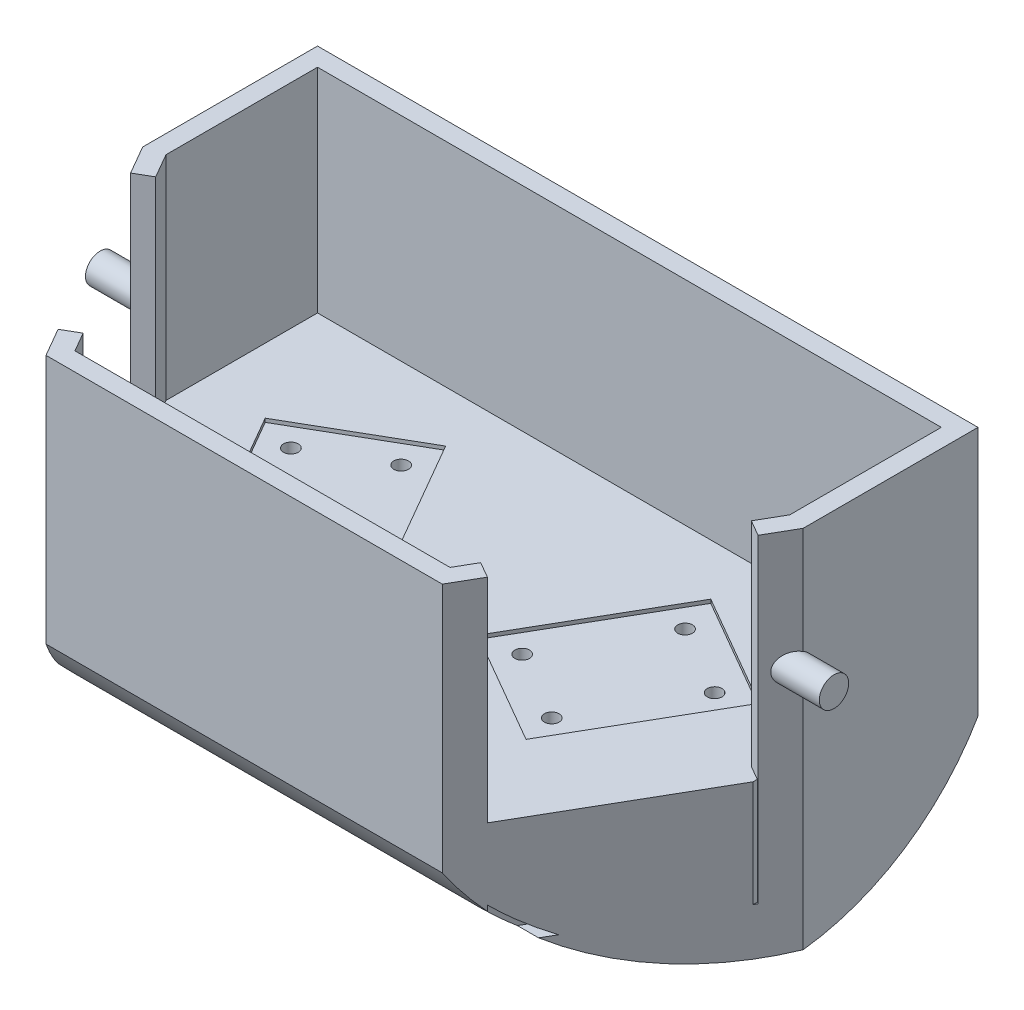
SolidWorks part; units mm, degrees
ref_plane "Front Plane" through (0, 0, 0) normal (0, 0, 1) x (1, 0, 0)
ref_plane "Top Plane" through (0, 0, 0) normal (0, 1, 0) x (1, 0, 0)
ref_plane "Right Plane" through (0, 0, 0) normal (1, 0, 0) x (0, 0, -1)
sketch "Sketch2" plane through (0, 0, 0) normal (0, 1, 0) x (1, 0, 0)
  line L0 (-54, -55) -> (-90, 7.3538)
  line L1 (-90, -55) -> (90, -55)
  line L2 (-90, -55) -> (-90, 55)
  line L3 (-90, 55) -> (90, 55)
  line L4 (90, -55) -> (90, 55)
  line L5 (-90, -55) -> (90, 55) construction
  line L6 (-90, 55) -> (90, -55) construction
  line L7 (0, -55) -> (0, 55) construction
  line L8 (54, -55) -> (90, 7.3538)
  point P0 (0, 0)
  dimension "D1" = 110
  dimension "D2" = 180
  dimension "D3" = 72
  dimension "D4" = 30
extrude "Boss-Extrude1" add sketch "Sketch2" along normal blind 50 and the other way blind 50 contours L1 L8 L4 L3 L2 L0 region at (0, 0, -4.375)
sketch "Sketch13" plane through (-90, 0, 0) normal (-1, 0, 0) x (0, 0, 1)
  line L0 (55, -50) -> (55, 50) construction
  line L1 (-55, -50) -> (55, -50)
  line L2 (-55, -50) -> (-55, -18.1472)
  line L3 (-55, -18.1472) -> (55, -18.1472)
  line L4 (55, -50) -> (55, -18.1472)
  line L5 (-55, -18.1472) -> (-55, -50)
  line L6 (-55, -50) -> (55, -50)
  line L7 (55, -50) -> (55, -18.1472)
  arc A1 (-55, -18.1472) -> (55, -18.1472) centre (0, 13.61) ccw
  point P8 (0, -49.9)
  line M1 (-7.3538, -50) -> (-7.3538, 50)
  line M3 (-55, 50) -> (-55, -50)
  line M4 (-55, -50) -> (-7.3538, -50)
  dimension "D1" = 63.51
  dimension "D2" = 0.1
extrude "Cut-Extrude9" cut sketch "Sketch13" against normal up to next contours A1 M3 M4 M1 | A1 L1 L4 M1 region at (-90, -41.0554, -42.0031) region at (-90, -41.1161, 41.7126)
shell "Shell1" thickness 5 removed face at (0, 50, -2.4513)
sketch "Sketch5" plane through (-64.3157, 0, 37.1327) normal (-0.866, 0, 0.5) x (0.5, 0, 0.866)
  line L0 (20.6314, 50) -> (-51.3686, 50) construction
  line L1 (-42.3686, 50) -> (11.6314, 50)
  line L2 (-42.3686, 50) -> (-42.3686, -37)
  line L3 (-42.3686, -37) -> (11.6314, -37)
  line L4 (11.6314, 50) -> (11.6314, -37)
  line L6 (20.6314, -18.1472) -> (20.6314, 50) construction
  dimension "D1" = 87
  dimension "D2" = 54
  dimension "D3" = 9
extrude "Cut-Extrude2" cut sketch "Sketch5" against normal blind 5
mirror "Mirror1" about plane through (0, 0, 0) normal (1, 0, 0) of "Cut-Extrude2"
sketch "Sketch16" plane through (-85, 0, 0) normal (1, 0, 0) x (0, 0, -1)
  line L0 (-55, -8) -> (55, -8)
  line L1 (-55, -18.1472) -> (-55, 50) construction
  line L2 (55, -18.1472) -> (55, 50) construction
  line L3 (-55, -8) -> (-55, -18.1472)
  line L4 (55, -8) -> (55, -18.1472)
  line L5 (7.3538, 50) -> (55, 50) construction
  arc A0 (-55, -18.1472) -> (55, -18.1472) centre (0, 20.3642) ccw
  dimension "D1" = 58
extrude "Boss-Extrude4" add sketch "Sketch16" along normal up to surface (170 mm away) up to face at (85, 8.5943, -30.1107)
sketch "Sketch6" plane through (0, -8, 0) normal (0, 1, 0) x (1, 0, 0)
  line L0 (-36.1276, 36.0441) -> (-12.8776, -4.2261)
  line L1 (-36.1276, 36.0441) -> (-67.3045, 18.0441)
  line L2 (-12.8776, -4.2261) -> (-44.0545, -22.2261)
  line L3 (-67.3045, 18.0441) -> (-44.0545, -22.2261)
  line L6 (-51.1132, -50) -> (-54.1699, -44.7058) construction
  line L13 (-38.6898, 26.4819) -> (-22.4398, -1.6639)
  line L14 (-22.4398, -1.6639) -> (-41.4923, -12.6639)
  line L15 (-57.7423, 15.4819) -> (-41.4923, -12.6639)
  line L16 (-38.6898, 26.4819) -> (-57.7423, 15.4819)
  line L17 (0, -55) -> (0, 55) construction
  line L18 (12.8776, -4.2261) -> (44.0545, -22.2261)
  line L19 (67.3045, 18.0441) -> (44.0545, -22.2261)
  line L20 (36.1276, 36.0441) -> (67.3045, 18.0441)
  line L21 (36.1276, 36.0441) -> (12.8776, -4.2261)
  circle A8 centre (-57.7423, 15.4819) radius 2
  circle A9 centre (-38.6898, 26.4819) radius 2
  circle A10 centre (-41.4923, -12.6639) radius 2
  circle A11 centre (-22.4398, -1.6639) radius 2
  circle A12 centre (22.4398, -1.6639) radius 2
  circle A13 centre (41.4923, -12.6639) radius 2
  circle A14 centre (38.6898, 26.4819) radius 2
  circle A15 centre (57.7423, 15.4819) radius 2
  dimension "D4" = 7
  dimension "D5" = 4
  dimension "D6" = 4
  dimension "D7" = 4
  dimension "D9" = 4
  dimension "D1" = 20
  dimension "D2" = 46.5
  dimension "D3" = 36
  dimension "D8" = 0.75
extrude "Cut-Extrude4" cut sketch "Sketch6" against normal through all contours A8 | A9 | A10 | A11 | A12 | A14 | A15 | A13
extrude "Cut-Extrude5" cut sketch "Sketch6<4>" against normal blind 1 contours L20 L21 L18 L19 A14 A12 A13 A15 | L0 L1 L3 L2 region at (40.091, -8, -6.909)
sketch "Sketch6<4>" plane through (0, -8, 0) normal (0, 1, 0) x (1, 0, 0) same geometry as "Sketch6"
sketch "Sketch17" plane through (0, -8, 0) normal (0, 1, 0) x (1, 0, 0)
  line L0 (-54, -55) -> (-85, -55)
  line L1 (-54, -55) -> (-85, -55) construction
  line L2 (-85, -55) -> (-85, -1.3064)
  line L3 (-85, -1.3064) -> (-54, -55)
  line L4 (85, -55) -> (54, -55)
  line L5 (54, -55) -> (85, -1.3064)
  line L6 (85, -1.3064) -> (85, -55)
extrude "Cut-Extrude10" cut sketch "Sketch17" against normal up to next
sketch "Sketch18" plane through (-90, 0, 0) normal (-1, 0, 0) x (0, 0, 1)
  line L0 (55, -18.1472) -> (55, 50) construction
  arc A0 (-55, -18.1472) -> (55, -18.1472) centre (0, 17.2426) ccw
  circle A1 centre (-5.7558, 17.2426) radius 4
  dimension "D1" = 8
extrude "Boss-Extrude5" add sketch "Sketch18" along normal blind 10 and the other way up to body separate body contours A1
mirror "Mirror2" about plane through (0, 0, 0) normal (1, 0, 0) of "Boss-Extrude5"
